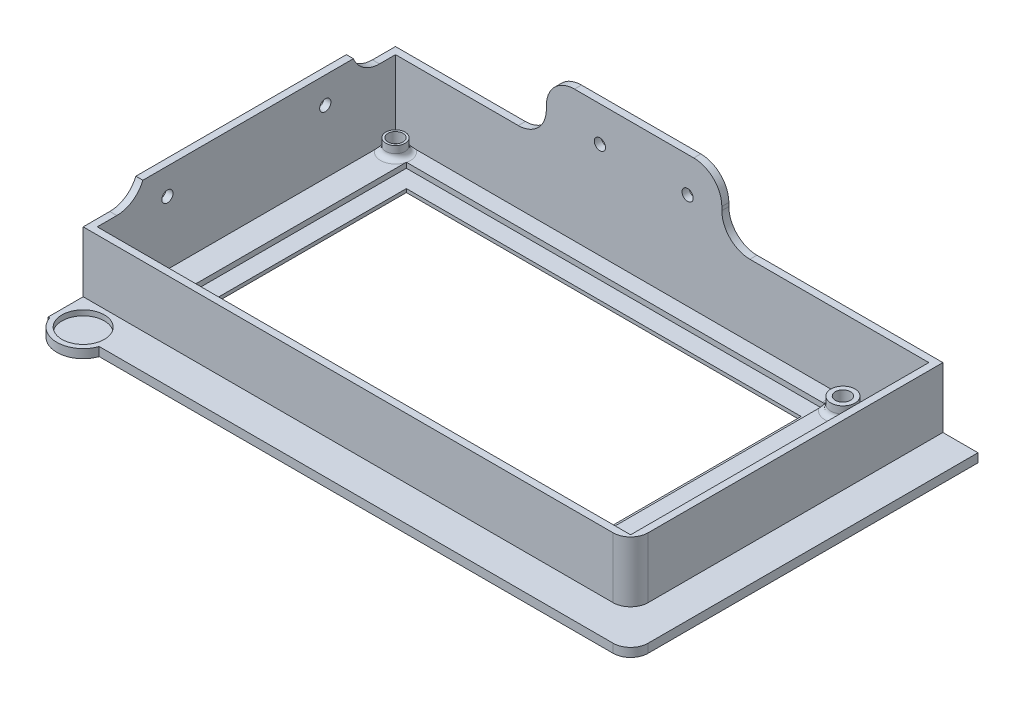
SolidWorks part; units mm, degrees
ref_plane "Alzado" through (0, 0, 0) normal (0, 0, 1) x (1, 0, 0)
ref_plane "Planta" through (0, 0, 0) normal (0, 1, 0) x (1, 0, 0)
ref_plane "Vista lateral" through (0, 0, 0) normal (1, 0, 0) x (0, 0, -1)
sketch "Croquis1" plane through (0, 0, 0) normal (0, 1, 0) x (1, 0, 0)
  line L1 (0, 0) -> (152, 0)
  line L2 (0, 0) -> (0, 85)
  line L3 (0, 85) -> (152, 85)
  line L4 (152, 0) -> (152, 85)
  dimension "D1" = 152
  dimension "D2" = 85
extrude "Saliente-Extruir1" add sketch "Croquis1" along normal blind 1.5
sketch "Croquis2" plane through (0, 1.5, 0) normal (0, 1, 0) x (1, 0, 0)
  line L0 (154, 87) -> (-2, 87)
  line L1 (-2, 87) -> (-2, -2)
  line L2 (-2, -2) -> (154, -2)
  line L3 (154, -2) -> (154, 87)
  line L4 (0, 85) -> (0, 0)
  line L5 (0, 0) -> (152, 0)
  line L6 (152, 0) -> (152, 85)
  line L7 (152, 85) -> (0, 85)
  line L8 (0, 85) -> (0, 0)
  line L9 (0, 0) -> (152, 0)
  line L10 (152, 0) -> (152, 85)
  line L11 (152, 85) -> (0, 85)
  dimension "D1" = 0
  dimension "D2" = 2
extrude "Saliente-Extruir3" add sketch "Croquis2" against normal up to surface (1.5 mm away) and the other way blind 5 up to face at (76, 0, -42.5)
sketch "Croquis3" plane through (0, 1.5, 0) normal (0, 1, 0) x (1, 0, 0)
  line L0 (0, 85) -> (0, 0) construction
  line L1 (152, 85) -> (0, 85) construction
  line L2 (76, 85) -> (76, 0) construction
  line L3 (0, 0) -> (152, 0) construction
  line L4 (0, 42.5) -> (152, 42.5) construction
  line L5 (0, 85) -> (0, 0) construction
  line L6 (152, 0) -> (152, 85) construction
  line L7 (0, 0) -> (152, 0) construction
  circle A0 centre (3.5, 81.5) radius 2.75
  circle A3 centre (3.5, 3.5) radius 3.45
  circle A4 centre (131, 81.5) radius 3.45
  circle A5 centre (131, 3.5) radius 3.45
  circle A6 centre (148.4, 3.5) radius 3.45
  circle A7 centre (148.4, 81.5) radius 3.45
  dimension "D1" = 5.5
  dimension "D4" = 6.9
  dimension "D2" = 3.5
  dimension "D3" = 3.5
  dimension "D5" = 127.5
  dimension "D6" = 3.5
  dimension "D7" = 3.5
  dimension "D8" = 3.5
  dimension "D9" = 3.5
  dimension "D10" = 127.5
  dimension "D11" = 3.6
extrude "Saliente-Extruir4" add sketch "Croquis3" along normal blind 3.5
sketch "Croquis4" plane through (0, 0, 0) normal (0, -1, 0) x (1, 0, 0)
  line L0 (-2, -87) -> (-2, 2) construction
  line L1 (7.6, -80.5) -> (127.1, -80.5)
  line L2 (7.6, -80.5) -> (7.6, -2)
  line L3 (7.6, -2) -> (127.1, -2)
  line L4 (127.1, -80.5) -> (127.1, -2)
  line L5 (154, -87) -> (-2, -87) construction
  dimension "D1" = 119.5
  dimension "D2" = 78.5
  dimension "D3" = 9.6
  dimension "D4" = 6.5
extrude "Cortar-Extruir1" cut sketch "Croquis4" against normal up to surface (1.5 mm away) up to face at (148.4, 1.5, -84.95)
sketch "Croquis5" plane through (0, 5, 0) normal (0, 1, 0) x (1, 0, 0)
  circle A0 centre (131, 3.5) radius 2.15
  circle A1 centre (3.5, 3.5) radius 2.15
  circle A2 centre (3.5, 81.5) radius 2.15
  circle A3 centre (131, 81.5) radius 2.15
  circle A4 centre (148.4, 3.5) radius 2.15
  circle A5 centre (148.4, 81.5) radius 2.15
  dimension "D1" = 4.3
extrude "Cortar-Extruir2" cut sketch "Croquis5" against normal blind 3
fillet "Redondeo1" radius 1.5 6 edges at (131, 1.5, -84.95) (3.5, 1.5, -84.25) (3.5, 1.5, -6.95) (131, 1.5, -6.95) (148.4, 1.5, -84.95) (148.4, 1.5, -6.95)
sketch "Croquis7" plane through (0, 6.5, 0) normal (0, 1, 0) x (1, 0, 0)
  line L0 (-2, -2) -> (154, -2) construction
  line L1 (0, 0) -> (152, 0) construction
  line L2 (0, 85) -> (0, 0) construction
  line L3 (-2, 87) -> (-2, -2) construction
  line L4 (152, 85) -> (0, 85) construction
  line L5 (154, 87) -> (-2, 87) construction
  line L6 (154, -2) -> (154, 87) construction
  line L7 (152, 0) -> (152, 85) construction
  line L8 (-2, -2) -> (86, -2)
  line L9 (0, 0) -> (86, 0)
  line L10 (0, 85) -> (0, 0)
  line L11 (-2, 87) -> (-2, -2)
  line L12 (152, 85) -> (0, 85)
  line L13 (154, 87) -> (-2, 87)
  line L14 (154, -2) -> (154, 87)
  line L15 (152, 0) -> (152, 85)
  line L16 (86, -2) -> (154, -2)
  line L21 (86, 0) -> (152, 0)
extrude "Saliente-Extruir5" add sketch "Croquis7" along normal blind 15.5
sketch "Croquis9" plane through (0, 22, 0) normal (0, 1, 0) x (1, 0, 0)
  line L0 (127.4996, 85) -> (5.9109, 85) construction
  line L1 (93, 85) -> (43, 85)
  line L2 (93, 85) -> (93, 87)
  line L3 (93, 87) -> (43, 87)
  line L4 (43, 85) -> (43, 87)
  line L5 (154, 87) -> (-2, 87) construction
  dimension "D1" = 50
  dimension "D2" = 45
extrude "Saliente-Extruir6" add sketch "Croquis9" along normal blind 17
sketch "Croquis10" plane through (0, 22, 0) normal (0, 1, 0) x (1, 0, 0)
  line L0 (0, 79.0891) -> (0, 7.0004) construction
  line L1 (0, 13) -> (-2, 13)
  line L2 (0, 13) -> (0, 73)
  line L3 (0, 73) -> (-2, 73)
  line L4 (-2, 13) -> (-2, 73)
  line L5 (-2, 87) -> (-2, -2) construction
  line L6 (-2, -2) -> (154, -2) construction
  dimension "D1" = 60
  dimension "D2" = 15
extrude "Saliente-Extruir7" add sketch "Croquis10" along normal blind 5
sketch "Croquis11" plane through (0, 0, 0) normal (1, 0, 0) x (0, 0, -1)
  line L0 (0, 22) -> (0, 1.5) construction
  line L1 (13, 27) -> (73, 27) construction
  circle A0 centre (20, 19.5) radius 1.6
  circle A1 centre (65, 19.5) radius 1.6
  dimension "D1" = 3.2
  dimension "D2" = 45
  dimension "D3" = 20
  dimension "D4" = 7.5
extrude "Cortar-Extruir4" cut sketch "Croquis11" against normal up to surface (2 mm away) up to face at (-2, 17.75, -42.75)
sketch "Croquis12" plane through (0, 0, -85) normal (0, 0, 1) x (1, 0, 0)
  line L0 (93, 39) -> (93, 22) construction
  line L2 (43, 39) -> (93, 39) construction
  circle A0 centre (83.25, 29) radius 1.6
  circle A1 centre (58.25, 29) radius 1.6
  dimension "D2" = 3.2
  dimension "D1" = 10
  dimension "D3" = 9.75
  dimension "D4" = 25
extrude "Cortar-Extruir5" cut sketch "Croquis12" against normal up to surface (2 mm away) up to face at (72, 20.75, -87)
fillet "Redondeo2" radius 8 6 edges at (-1, 22, -73) (-1, 22, -13) (93, 39, -86) (43, 39, -86) (43, 22, -86) (93, 22, -86)
sketch "Croquis13" plane through (0, 0, 2) normal (0, 0, 1) x (1, 0, 0)
  line L0 (-2, 22) -> (-2, 0) construction
  line L1 (-2, 4.75) -> (154, 4.75)
  line L2 (-2, 4.75) -> (-2, 2.25)
  line L3 (-2, 2.25) -> (154, 2.25)
  line L4 (154, 4.75) -> (154, 2.25)
  line L5 (154, 22) -> (154, 0) construction
  line L6 (-2, 0) -> (154, 0) construction
  dimension "D1" = 2.5
  dimension "D2" = 2.25
extrude "Saliente-Extruir8" add sketch "Croquis13" along normal blind 10
sketch "Croquis14" plane through (154, 0, 0) normal (1, 0, 0) x (0, 0, -1)
  line L0 (87, 22) -> (87, 0) construction
  line L1 (-12, 4.75) -> (87, 4.75)
  line L2 (-12, 4.75) -> (-12, 2.25)
  line L3 (-12, 2.25) -> (87, 2.25)
  line L4 (87, 4.75) -> (87, 2.25)
  line L5 (-12, 2.25) -> (-2, 2.25) construction
extrude "Saliente-Extruir9" add sketch "Croquis14" along normal blind 10
fillet "Redondeo3" radius 5 2 edges at (154, 1.125, 2) (164, 3.5, 12)
sketch "Croquis15" plane through (0, 4.75, 0) normal (0, 1, 0) x (1, 0, 0)
  line L4 (-2, -2) -> (149, -2) construction
  line L5 (-2, -12) -> (-2, -2) construction
  circle A0 centre (5.5, -9.5) radius 7.5
  dimension "D1" = 15
extrude "Saliente-Extruir10" add sketch "Croquis15" against normal up to surface (2.5 mm away) up to face at (117.7589, 2.25, -17.4911)
sketch "Croquis16" plane through (0, 4.75, 0) normal (0, 1, 0) x (1, 0, 0)
  arc A1 (-1.5711, -12) -> (12.5711, -12) centre (5.5, -9.5) ccw construction
  arc A3 (-1.5711, -12) -> (12.5711, -12) centre (5.5, -9.5) ccw construction
  circle A4 centre (5.5, -9.5) radius 6.05
  dimension "D1" = 12.1
extrude "Cortar-Extruir6" cut sketch "Croquis16" against normal blind 1.5
sketch "Croquis17" plane through (0, 0, 0) normal (0, -1, 0) x (1, 0, 0)
  line L0 (127.1, -2) -> (7.6, -2) construction
  line L1 (127.1, -80.5) -> (127.1, -2) construction
  line L2 (7.6, -2) -> (7.6, -80.5) construction
  line L3 (7.6, -80.5) -> (127.1, -80.5) construction
  line L4 (154, -87) -> (154, -3)
  line L5 (149, 2) -> (-2, 2)
  line L6 (-2, 2) -> (-2, -87)
  line L7 (-2, -87) -> (154, -87)
  line L8 (154, -87) -> (154, -3)
  line L9 (149, 2) -> (-2, 2)
  line L10 (-2, 2) -> (-2, -87)
  line L11 (-2, -87) -> (154, -87)
  line L12 (7.6, -80.5) -> (127.1, -80.5)
  line L13 (7.6, -2) -> (7.6, -80.5)
  line L14 (127.1, -80.5) -> (127.1, -2)
  line L15 (127.1, -2) -> (7.6, -2)
  arc A1 (154, -3) -> (149, 2) centre (149, -3) ccw
  arc A2 (154, -3) -> (149, 2) centre (149, -3) ccw
  dimension "D1" = 0
extrude "Saliente-Extruir11" add sketch "Croquis17" along normal blind 1
sketch "Croquis18" plane through (0, -1, 0) normal (0, -1, 0) x (1, 0, 0)
  line L0 (7.6, -2) -> (7.6, -80.5) construction
  line L1 (127.1, -80.5) -> (7.6, -80.5)
  line L2 (127.1, -80.5) -> (127.1, -75.5)
  line L3 (127.1, -75.5) -> (7.6, -75.5)
  line L4 (7.6, -80.5) -> (7.6, -75.5)
  line L6 (7.6, -2) -> (12.6, -2)
  line L7 (7.6, -2) -> (7.6, -75.5)
  line L8 (7.6, -75.5) -> (12.6, -75.5)
  line L9 (12.6, -2) -> (12.6, -75.5)
  line L10 (127.1, -2) -> (12.6, -2)
  line L11 (127.1, -2) -> (127.1, -4)
  line L12 (127.1, -4) -> (12.6, -4)
  line L13 (12.6, -2) -> (12.6, -4)
  line L14 (127.1, -4) -> (125.1, -4)
  line L15 (127.1, -4) -> (127.1, -75.5)
  line L16 (127.1, -75.5) -> (125.1, -75.5)
  line L17 (125.1, -4) -> (125.1, -75.5)
  line M11 (7.6, -80.5) -> (7.6, -2)
  line M12 (7.6, -2) -> (127.1, -2)
  line M13 (127.1, -2) -> (127.1, -80.5)
  line M14 (127.1, -80.5) -> (7.6, -80.5)
  dimension "D1" = 5
  dimension "D2" = 5
  dimension "D3" = 2
  dimension "D4" = 2
extrude "Saliente-Extruir12" add sketch "Croquis18" against normal blind 1 contours L12 L9 M13 M12 | L12 L17 L3 M13 | L3 M13 M11 M14 | L9 L3 M12 M11 region at (67.35, -1, -78) region at (126.1, -1, -39.75) region at (10.1, -1, -38.75) region at (69.85, -1, -3)
